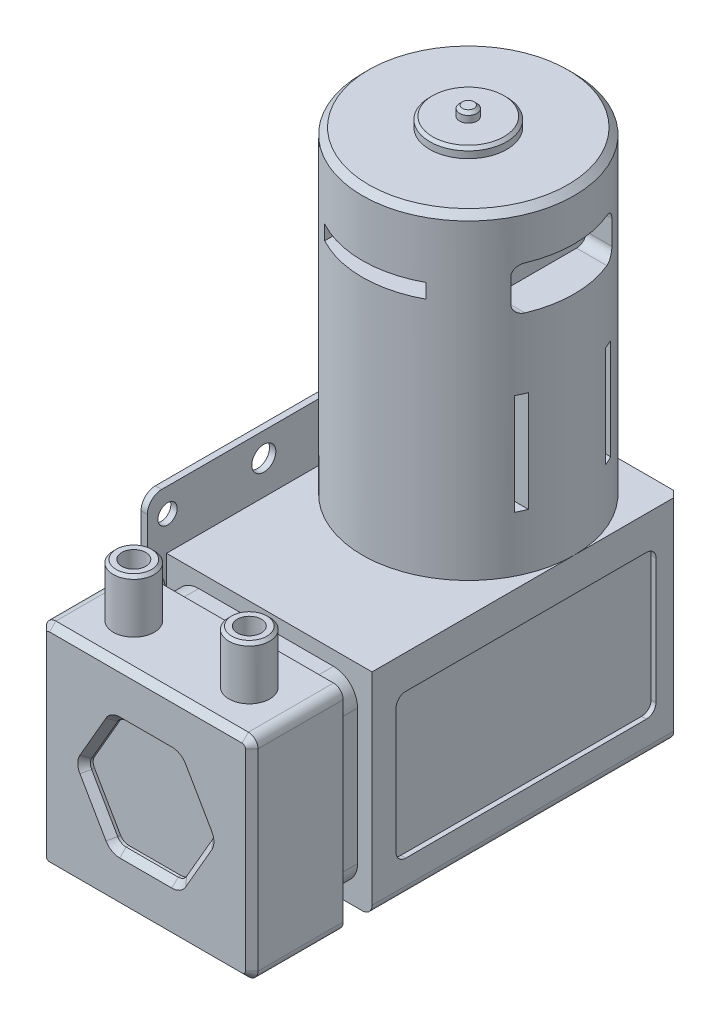
SolidWorks part; units mm, degrees
material "合金钢"
ref_plane "前视基准面" through (0, 0, 0) normal (0, 0, 1) x (1, 0, 0)
ref_plane "上视基准面" through (0, 0, 0) normal (0, 1, 0) x (1, 0, 0)
ref_plane "右视基准面" through (0, 0, 0) normal (1, 0, 0) x (0, 0, -1)
sketch "草图1" plane through (0, 0, 0) normal (1, 0, 0) x (0, 0, -1)
  line L1 (-44.5, 22) -> (44.5, 22)
  line L2 (-44.5, 22) -> (-44.5, -22)
  line L3 (-44.5, -22) -> (44.5, -22)
  line L4 (44.5, 22) -> (44.5, -22)
  line L5 (-44.5, 22) -> (44.5, -22) construction
  line L6 (-44.5, -22) -> (44.5, 22) construction
  point P0 (0, 0)
  dimension "D1" = 89
  dimension "D2" = 44
extrude "凸台-拉伸1" add sketch "草图1" along normal blind 44
sketch "草图2" plane through (0, 22, 0) normal (0, 1, 0) x (1, 0, 0)
  line L0 (44, 44.5) -> (0, 44.5) construction
  line L1 (44, 44.5) -> (44, -44.5) construction
  line L2 (0, 44.5) -> (0, -44.5) construction
  circle A0 centre (22, 22.5) radius 22
extrude "凸台-拉伸2" add sketch "草图2" along normal blind 66
ref_plane "基准面1" through (0, 0, 25.5) normal (0, 0, 1) x (1, 0, 0)
sketch "草图3" plane through (0, 0, 25.5) normal (0, 0, 1) x (1, 0, 0)
  line L0 (44, 22) -> (0, 22) construction
  line L1 (3, -19) -> (41, -19)
  line L2 (3, -19) -> (3, 19)
  line L3 (3, 19) -> (41, 19)
  line L4 (41, -19) -> (41, 19)
  line L5 (3, -19) -> (41, 19) construction
  line L6 (3, 19) -> (41, -19) construction
  line L7 (44, -22) -> (0, -22) construction
  line L8 (44, 22) -> (44, -22) construction
  line L9 (0, 22) -> (0, -22) construction
  point P0 (22, 0)
  dimension "D1" = 3
  dimension "D2" = 3
  dimension "D3" = 3
  dimension "D4" = 3
extrude "切除-拉伸1" cut sketch "草图3" against normal blind 6 flip side to cut
sketch "草图4" plane through (44, 0, 0) normal (1, 0, 0) x (0, 0, -1)
  line L0 (44.5, 88) -> (0.5, 88) construction
  line L1 (12, 78) -> (33, 78)
  line L2 (12, 78) -> (12, 69)
  line L3 (12, 69) -> (33, 69)
  line L4 (33, 78) -> (33, 69)
  line L5 (12, 78) -> (33, 69) construction
  line L6 (12, 69) -> (33, 78) construction
  line L7 (14.5, 54.5) -> (12.5, 54.5)
  line L8 (14.5, 54.5) -> (14.5, 33.5)
  line L9 (14.5, 33.5) -> (12.5, 33.5)
  line L10 (12.5, 54.5) -> (12.5, 33.5)
  line L11 (14.5, 54.5) -> (12.5, 33.5) construction
  line L12 (14.5, 33.5) -> (12.5, 54.5) construction
  line L13 (30.5, 54.5) -> (32.5, 54.5)
  line L14 (30.5, 54.5) -> (30.5, 33.5)
  line L15 (30.5, 33.5) -> (32.5, 33.5)
  line L16 (32.5, 54.5) -> (32.5, 33.5)
  line L17 (30.5, 54.5) -> (32.5, 33.5) construction
  line L18 (30.5, 33.5) -> (32.5, 54.5) construction
  line L19 (44.5, -22) -> (44.5, 22) construction
  line L20 (0.5, 88) -> (0.5, 22) construction
  point P0 (22.5, 73.5)
  point P5 (13.5, 44)
  point P10 (31.5, 44)
  dimension "D1" = 10
  dimension "D2" = 9
  dimension "D3" = 21
  dimension "D4" = 25
  dimension "D5" = 2
  dimension "D6" = 21
  dimension "D7" = 12
  dimension "D8" = 12
extrude "切除-拉伸2" cut sketch "草图4" against normal blind 8
ref_plane "基准面2" through (22, 0, 0) normal (1, 0, 0) x (0, 0, -1)
mirror "镜向1" about plane through (22, 0, 0) normal (1, 0, 0) of "切除-拉伸2"
sketch "草图5" plane through (0, 88, 0) normal (0, 1, 0) x (1, 0, 0)
  circle A0 centre (22, 22.5) radius 8
  dimension "D1" = 16
extrude "凸台-拉伸3" add sketch "草图5" along normal blind 2
sketch "草图6" plane through (0, 90, 0) normal (0, 1, 0) x (1, 0, 0)
  circle A0 centre (22, 22.5) radius 1.8
  dimension "D1" = 3.6
extrude "凸台-拉伸4" add sketch "草图6" along normal blind 2
sketch "草图7" plane through (0, 22, 0) normal (0, 1, 0) x (1, 0, 0)
  line L0 (44, -25.5) -> (44, -44.5) construction
  circle A0 centre (34, -35) radius 4.25
  circle A1 centre (34, -35) radius 2.5
  point P4 (44, -35)
  dimension "D1" = 8.5
  dimension "D2" = 10
  dimension "D3" = 5
extrude "凸台-拉伸5" add sketch "草图7" along normal blind 11
mirror "镜向2" about plane through (22, 0, 0) normal (1, 0, 0) of "凸台-拉伸5"
sketch "草图8" plane through (44, 0, 0) normal (1, 0, 0) x (0, 0, -1)
  line L0 (44.5, -22) -> (44.5, 22) construction
  line L1 (-14.5, -15) -> (39.5, -15)
  line L2 (-14.5, -15) -> (-14.5, 15)
  line L3 (-14.5, 15) -> (39.5, 15)
  line L4 (39.5, -15) -> (39.5, 15)
  line L5 (-14.5, -15) -> (39.5, 15) construction
  line L6 (-14.5, 15) -> (39.5, -15) construction
  line L7 (-19.5, 22) -> (-19.5, -22) construction
  line L8 (-19.5, -22) -> (44.5, -22) construction
  line L9 (44.5, 22) -> (22.5, 22) construction
  point P0 (12.5, 0)
  dimension "D1" = 5
  dimension "D2" = 5
  dimension "D3" = 7
  dimension "D4" = 7
extrude "切除-拉伸3" cut sketch "草图8" against normal blind 1
mirror "镜向3" about plane through (22, 0, 0) normal (1, 0, 0) of "切除-拉伸3"
sketch "草图9" plane through (0, 0, -44.5) normal (0, 0, -1) x (-1, 0, 0)
  line L0 (-44, -22) -> (0, -22) construction
  line L1 (-8.86, 0) -> (-15.43, 11.3796)
  line L2 (-15.43, 11.3796) -> (-28.57, 11.3796)
  line L3 (-28.57, 11.3796) -> (-35.14, 0)
  line L4 (-35.14, 0) -> (-28.57, -11.3796)
  line L5 (-28.57, -11.3796) -> (-15.43, -11.3796)
  line L6 (-15.43, -11.3796) -> (-8.86, 0)
  circle A0 centre (-22, 0) radius 11.3796 construction
  point P12 (-22, -22)
  dimension "D1" = 13.14
extrude "切除-拉伸4" cut sketch "草图9" against normal blind 1.888
mirror "镜向4" about plane through (0, 0, 0) normal (0, 0, 1) of "切除-拉伸4"
sketch "草图10" plane through (0, 0, -44.5) normal (0, 0, -1) x (-1, 0, 0)
  line L0 (0, 88) -> (-44, 88) construction
  line L1 (-32.5, 75) -> (-11.5, 75)
  line L2 (-32.5, 75) -> (-32.5, 72)
  line L3 (-32.5, 72) -> (-11.5, 72)
  line L4 (-11.5, 75) -> (-11.5, 72)
  line L5 (-32.5, 75) -> (-11.5, 72) construction
  line L6 (-32.5, 72) -> (-11.5, 75) construction
  point P0 (-22, 73.5)
  dimension "D1" = 3
  dimension "D2" = 21
  dimension "D3" = 13
extrude "切除-拉伸5" cut sketch "草图10" against normal blind 6
ref_plane "基准面3" through (0, 0, -22.5) normal (0, 0, -1) x (-1, 0, 0)
mirror "镜向5" about plane through (0, 0, -22.5) normal (0, 0, -1) of "切除-拉伸5"
sketch "草图11" plane through (0, -22, 0) normal (0, -1, 0) x (-1, 0, 0)
  line L0 (0, -19.5) -> (-44, -19.5) construction
  line L1 (-8.5, -13.5) -> (-35.5, -13.5)
  line L2 (-8.5, -13.5) -> (-8.5, 8.5)
  line L3 (-8.5, 8.5) -> (-35.5, 8.5)
  line L4 (-35.5, -13.5) -> (-35.5, 8.5)
  line L5 (-8.5, -13.5) -> (-35.5, 8.5) construction
  line L6 (-8.5, 8.5) -> (-35.5, -13.5) construction
  line L7 (-8.5, 16.5) -> (-35.5, 16.5)
  line L8 (-8.5, 16.5) -> (-8.5, 38.5)
  line L9 (-8.5, 38.5) -> (-35.5, 38.5)
  line L10 (-35.5, 16.5) -> (-35.5, 38.5)
  line L11 (-8.5, 16.5) -> (-35.5, 38.5) construction
  line L12 (-8.5, 38.5) -> (-35.5, 16.5) construction
  line L13 (-44, 44.5) -> (0, 44.5) construction
  point P0 (-22, -2.5)
  point P5 (-22, 27.5)
  point P15 (-22, 44.5)
  dimension "D1" = 6
  dimension "D2" = 6
  dimension "D3" = 8
  dimension "D4" = 27
extrude "切除-拉伸6" cut sketch "草图11" against normal blind 1.234
fillet "圆角1" radius 5 4 edges at (41, -19, 22.5) (3, 19, 22.5) (3, -19, 22.5) (41, 19, 22.5)
fillet "圆角2" radius 2 36 edges at (15.43, -11.3796, 43.556) (35.14, 0, 43.556) (28.57, 11.3796, 43.556) (15.43, 11.3796, 43.556) (8.86, 0, 43.556) (28.57, -11.3796, 43.556) (5.3337, 78, -12) (5.3337, 78, -33) (5.3337, 69, -33) (5.3337, 69, -12) (38.6663, 69, -12) (38.6663, 78, -33) (38.6663, 78, -12) (38.6663, 69, -33) (8.5, -21.383, -16.5) (8.5, -21.383, -38.5) (35.5, -21.383, -38.5) (35.5, -21.383, -16.5) (8.5, -21.383, 13.5) (8.5, -21.383, -8.5) (35.5, -21.383, -8.5) (35.5, -21.383, 13.5) (0.5, -15, -39.5) (0.5, 15, 14.5) (0.5, 15, -39.5) (0.5, -15, 14.5) (43.5, 15, -39.5) (43.5, 15, 14.5) (43.5, -15, 14.5) (43.5, -15, -39.5) (15.43, 11.3796, -43.556) (28.57, 11.3796, -43.556) (35.14, 0, -43.556) (28.57, -11.3796, -43.556) (15.43, -11.3796, -43.556) (8.86, 0, -43.556)
chamfer "倒角1" distance 0.6 angle 45 2 edges at (10, 33, 39.25) (34, 33, 39.25)
chamfer "倒角2" distance 1.314 angle 45 1 edges at (22, 88, -0.5)
fillet "圆角3" radius 2 6 edges at (44, -22, -12.5) (0, -22, -12.5) (0, 22, 35) (0, -22, 35) (44, -22, 35) (44, 22, 35)
chamfer "倒角3" distance 1.314 angle 45 37 edges at (0.5858, -21.4142, -44.5) (22, -22, -44.5) (43.4142, -21.4142, -44.5) (44, 1, -44.5) (0, 1, -44.5) (15.5847, 11.1116, -44.5) (22, 11.3796, -44.5) (28.4153, 11.1116, -44.5) (31.855, 5.6898, -44.5) (34.8306, 0, -44.5) (31.855, -5.6898, -44.5) (28.4153, -11.1116, -44.5) (22, -11.3796, -44.5) (15.5847, -11.1116, -44.5) (12.145, -5.6898, -44.5) (9.1694, 0, -44.5) (12.145, 5.6898, -44.5) (28.4153, -11.1116, 44.5) (31.855, -5.6898, 44.5) (34.8306, 0, 44.5) (31.855, 5.6898, 44.5) (28.4153, 11.1116, 44.5) (22, 11.3796, 44.5) (15.5847, 11.1116, 44.5) (12.145, 5.6898, 44.5) (9.1694, 0, 44.5) (12.145, -5.6898, 44.5) (15.5847, -11.1116, 44.5) (22, -11.3796, 44.5) (43.4142, 21.4142, 44.5) (44, 0, 44.5) (43.4142, -21.4142, 44.5) (22, -22, 44.5) (0.5858, -21.4142, 44.5) (0, 0, 44.5) (0.5858, 21.4142, 44.5) (22, 22, 44.5)
chamfer "倒角4" distance 0.6 angle 45 2 edges at (22, 92, -20.7) (22, 90, -14.5)
sketch "草图12" plane through (0, 0, 0) normal (-1, 0, 0) x (0, 0, 1)
  line L1 (23.5, 22) -> (-22.5, 22)
  line L2 (23.5, 22) -> (23.5, 34)
  line L3 (23.5, 34) -> (-22.5, 34)
  line L4 (-22.5, 22) -> (-22.5, 34)
  dimension "D1" = 12
  dimension "D2" = 46
extrude "凸台-拉伸6" add sketch "草图12" against normal blind 1.314
sketch "草图13" plane through (0, 0, 0) normal (-1, 0, 0) x (0, 0, 1)
  line L0 (23.5, 34) -> (23.5, 22) construction
  line L1 (23.5, 34) -> (-22.5, 34) construction
  circle A0 centre (19.3, 29) radius 2
  circle A1 centre (-0.7, 29) radius 2.5
  dimension "D1" = 4
  dimension "D2" = 5
  dimension "D3" = 4.2
  dimension "D4" = 5
  dimension "D5" = 20
extrude "切除-拉伸7" cut sketch "草图13" against normal up to next
fillet "圆角4" radius 10 1 edges at (0.657, 22, 19.5)
fillet "圆角5" radius 3 2 edges at (0.657, 22, 23.5) (0.657, 34, 23.5)
